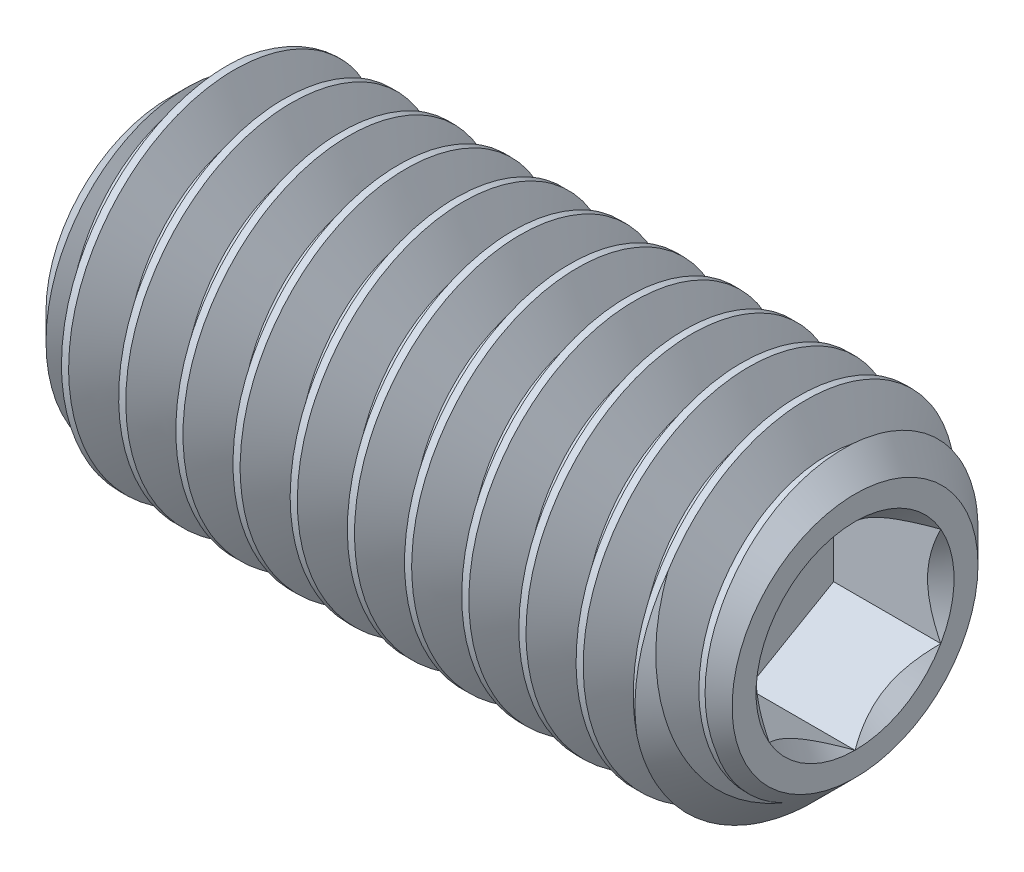
SolidWorks part; units mm, degrees
material "Alloy Steel"
ref_plane "Front" through (0, 0, 0) normal (0, 0, 1) x (1, 0, 0)
ref_plane "Top" through (0, 0, 0) normal (0, 1, 0) x (1, 0, 0)
ref_plane "Right" through (0, 0, 0) normal (1, 0, 0) x (0, 0, -1)
sketch "Sketch1" plane through (0, 0, 0) normal (0, 0, 1) x (1, 0, 0)
  line L0 (3, 0) -> (-3, 0) construction
  dimension "Length" = 6
ref_plane "Plane1" through (3, 0, 0) normal (1, 0, 0) x (0, 0, -1)
sketch "Sketch2" plane through (3, 0, 0) normal (1, 0, 0) x (0, 0, -1)
  circle A0 centre (0, 0) radius 1.5
  dimension "OD" = 3
extrude "Extrude1" add sketch "Sketch2" against normal up to vertex (6 mm away) up to point (-3, 0, 0)
sketch "Sketch3" plane through (3, 0, 0) normal (1, 0, 0) x (0, 0, -1)
  circle A1 centre (0, 0) radius 1.5
  circle A2 centre (0, 0) radius 1.5
  dimension "D1" = 0
curve "Helix/Spiral1" pitch 0.5 height 9 turns 18 parameters "Pitch"=0.5
sketch "Sketch4" plane through (0, 0, 0) normal (0, 0, 1) x (1, 0, 0)
  line L0 (3.4375, 1.5) -> (3, 1.5)
  line L1 (3, 1.5) -> (3.1875, 1.1752)
  line L2 (3.1875, 1.1752) -> (3.25, 1.1752)
  line L3 (3.25, 1.1752) -> (3.4375, 1.5)
  line L4 (3.3437, 1.3376) -> (3.0937, 1.3376) construction
  line L5 (3.2187, 1.1752) -> (3.2187, 1.5) construction
  line L6 (3, -1.5) -> (3, 1.5) construction
  line L7 (3, 1.5) -> (3, -1.5) construction
  line L8 (0, 0) -> (3, 0) construction
  line L9 (-3, 1.5) -> (-3, -1.5) construction
  point P18 (0.75, -1.5)
  dimension "D1" = 60
  dimension "D2" = 0.0625
  dimension "D3" = 0.25
  dimension "D4" = 3
  dimension "D5" = 2.25
sweep "Cut-Sweep1" cut profiles "Sketch4" path "Helix/Spiral1"
sketch "Sketch5" plane through (3, 0, 0) normal (1, 0, 0) x (0, 0, -1)
  circle A0 centre (0, 0) radius 1.1752 construction
  circle A1 centre (0, 0) radius 1.0752
  dimension "D1" = 0.1
extrude "Cut-Extrude1" cut sketch "Sketch5" against normal through all draft 45 flip side to cut
sketch "Sketch6" plane through (-3, 0, 0) normal (-1, 0, 0) x (0, 0, 1)
  circle A1 centre (0, 0) radius 1.0752
  circle A2 centre (0, 0) radius 1.0752
  dimension "D1" = 0
extrude "Cut-Extrude2" cut sketch "Sketch6" against normal through all draft 45 flip side to cut
sketch "Sketch8" plane through (3, 0, 0) normal (1, 0, 0) x (0, 0, -1)
  line L1 (0, 0.866) -> (-0.75, 0.433)
  line L2 (-0.75, 0.433) -> (-0.75, -0.433)
  line L3 (-0.75, -0.433) -> (0, -0.866)
  line L4 (0, -0.866) -> (0.75, -0.433)
  line L5 (0.75, -0.433) -> (0.75, 0.433)
  line L6 (0.75, 0.433) -> (0, 0.866)
  circle A0 centre (0, 0) radius 0.75 construction
  dimension "Hex" = 1.5
extrude "Cut-Extrude3" cut sketch "Sketch8" against normal blind 0.9375
sketch "Sketch9" plane through (3, 0, 0) normal (1, 0, 0) x (0, 0, -1)
  circle A0 centre (0, 0) radius 0.866
extrude "Cut-Extrude4" cut sketch "Sketch9" against normal blind 0.9375 draft 45
equation "\"D3@Helix/Spiral1\" = \"Length@Sketch1\"+3"
equation "\"D2@Sketch4\" = \"Pitch@Helix/Spiral1\"*.125"
equation "\"D3@Sketch4\" = \"Pitch@Helix/Spiral1\"*.5"
equation "\"D1@Cut-Extrude3\" = \"Hex@Sketch8\"*.625"
equation "\"D1@Cut-Extrude4\" = \"D1@Cut-Extrude3\""
equation "\"D4@Sketch4\" = \"OD@Sketch2\""
equation "\"D5@Sketch4\" = \"Pitch@Helix/Spiral1\"*4.5"
